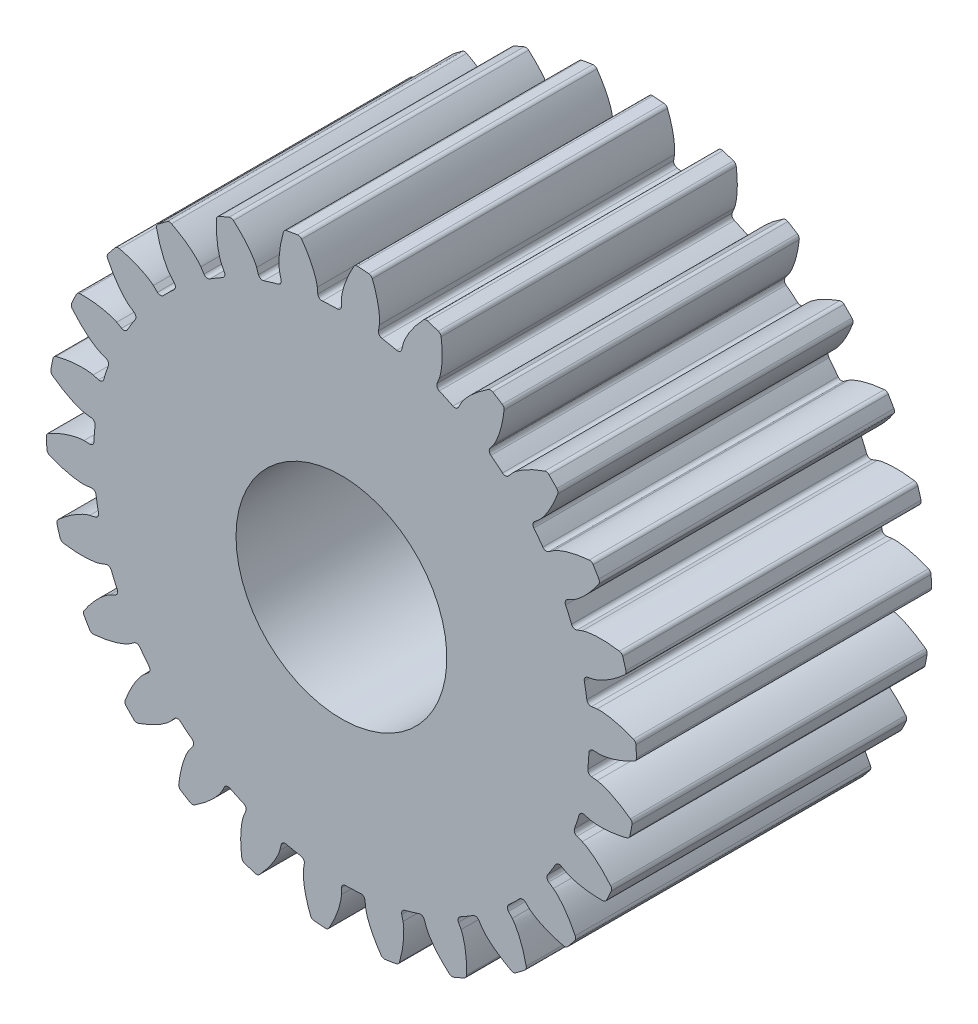
SolidWorks part; units mm, degrees
ref_plane "Front Plane" through (0, 0, 0) normal (0, 0, 1) x (1, 0, 0)
ref_plane "Top Plane" through (0, 0, 0) normal (0, 1, 0) x (1, 0, 0)
ref_plane "Right Plane" through (0, 0, 0) normal (1, 0, 0) x (0, 0, -1)
sketch "Involute Geometry" plane through (0, 0, 0) normal (0, 0, 1) x (1, 0, 0)
  line L0 (0, 12.216) -> (0, 0) construction
  line L1 (0, 0) -> (1.0333, 13.9618) construction
  line L2 (1.7984, 12.0829) -> (0, 0) construction
  line L3 (0.175, 12.9988) -> (0, 0) construction
  line L4 (0, 0) -> (1.7406, 12.883) construction
  circle A1 centre (0, 0) radius 12.216 construction
  circle A2 centre (0, 0) radius 13 construction
  circle A3 centre (0, 0) radius 14 construction
  circle A4 centre (0, 0) radius 11.75 construction
  arc A5 (0.6454, 13.9851) -> (1.4204, 13.9278) centre (0, 0) cw
  arc A6 (0.175, 12.9988) -> (1.7406, 12.883) centre (0, 0) cw construction
  spline S0 degree 4 poles (0, 12.216) (0, 12.2259) (0.0007, 12.2537) (0.0046, 12.3061) (0.0149, 12.3914) (0.0336, 12.4994) (0.064, 12.638) (0.108, 12.7997) (0.1647, 12.9755) (0.2354, 13.1642) (0.3138, 13.35) (0.3992, 13.5328) (0.4907, 13.7124) (0.6089, 13.9268) (0.7611, 14.1794) (0.9535, 14.4672) (1.1888, 14.7846) (1.4461, 15.0973) (1.7136, 15.3959) (1.9994, 15.6864) (2.287, 15.9594) (2.6008, 16.2305) (2.8982, 16.4744) (3.2472, 16.733) (3.5335, 16.9374) (3.9271, 17.1908) (4.1642, 17.3355) (4.4469, 17.4991) (4.5752, 17.5686) (4.654, 17.6115) knots 0 0 0 0 0 0.005377 0.015084 0.028532 0.04661 0.064855 0.092111 0.119476 0.146842 0.174209 0.201575 0.228941 0.256307 0.307035 0.361767 0.4165 0.471232 0.525964 0.580697 0.635429 0.690161 0.744894 0.799626 0.854358 0.909091 0.954545 1 1 1 1 1 construction
  spline S1 degree 4 poles (0, 12.216) (0, 12.2259) (0.0007, 12.2537) (0.0046, 12.3061) (0.0149, 12.3914) (0.0336, 12.4994) (0.064, 12.638) (0.108, 12.7997) (0.1647, 12.9755) (0.2354, 13.1642) (0.3138, 13.35) (0.3992, 13.5328) (0.4907, 13.7124) (0.6089, 13.9268) (0.7611, 14.1794) (0.9535, 14.4672) (1.1888, 14.7846) (1.4461, 15.0973) (1.7136, 15.3959) (1.9994, 15.6864) (2.287, 15.9594) (2.6008, 16.2305) (2.8982, 16.4744) (3.2472, 16.733) (3.5335, 16.9374) (3.8418, 17.1359) (3.9936, 17.2306) (4.0719, 17.2782) knots 0 0 0 0 0 0.005377 0.015084 0.028532 0.04661 0.064855 0.092111 0.119476 0.146842 0.174209 0.201575 0.228941 0.256307 0.307035 0.361767 0.4165 0.471232 0.525964 0.580697 0.635429 0.690161 0.744894 0.799626 0.854358 0.909091 0.909091 0.909091 0.909091 0.909091
  spline S3 degree 4 poles (1.7984, 12.0829) (1.7999, 12.0927) (1.8033, 12.1203) (1.8071, 12.1727) (1.8095, 12.2586) (1.8069, 12.3682) (1.7972, 12.5097) (1.7775, 12.6762) (1.7473, 12.8584) (1.7051, 13.0554) (1.655, 13.2507) (1.5974, 13.4441) (1.5334, 13.6352) (1.448, 13.8647) (1.3347, 14.1369) (1.1867, 14.45) (1.0007, 14.7985) (0.7922, 15.1457) (0.5716, 15.4804) (0.3317, 15.8098) (0.0874, 16.1222) (-0.1831, 16.4365) (-0.4413, 16.7215) (-0.7484, 17.0287) (-1.0015, 17.2731) (-1.3535, 17.5817) (-1.5667, 17.7597) (-1.8223, 17.9631) (-1.9389, 18.0507) (-2.0106, 18.1047) knots 0 0 0 0 0 0.005377 0.015084 0.028532 0.04661 0.064855 0.092111 0.119476 0.146842 0.174209 0.201575 0.228941 0.256307 0.307035 0.361767 0.4165 0.471232 0.525964 0.580697 0.635429 0.690161 0.744894 0.799626 0.854358 0.909091 0.954545 1 1 1 1 1 construction
  spline S4 degree 4 poles (1.7984, 12.0829) (1.7999, 12.0927) (1.8033, 12.1203) (1.8071, 12.1727) (1.8095, 12.2586) (1.8069, 12.3682) (1.7972, 12.5097) (1.7775, 12.6762) (1.7473, 12.8584) (1.7051, 13.0554) (1.655, 13.2507) (1.5974, 13.4441) (1.5334, 13.6352) (1.448, 13.8647) (1.3347, 14.1369) (1.1867, 14.45) (1.0007, 14.7985) (0.7922, 15.1457) (0.5716, 15.4804) (0.3317, 15.8098) (0.0874, 16.1222) (-0.1831, 16.4365) (-0.4413, 16.7215) (-0.7484, 17.0287) (-1.0015, 17.2731) (-1.2772, 17.5148) (-1.4134, 17.6308) (-1.4839, 17.6894) knots 0 0 0 0 0 0.005377 0.015084 0.028532 0.04661 0.064855 0.092111 0.119476 0.146842 0.174209 0.201575 0.228941 0.256307 0.307035 0.361767 0.4165 0.471232 0.525964 0.580697 0.635429 0.690161 0.744894 0.799626 0.854358 0.909091 0.909091 0.909091 0.909091 0.909091
  dimension "D5" = 6.923
sketch "Sketch2" plane through (0, 0, 0) normal (0, 0, 1) x (1, 0, 0)
  circle A0 centre (0, 0) radius 11.75 construction
  circle A1 centre (0, 0) radius 11.75
extrude "Boss-Extrude1" add sketch "Sketch2" along normal mid plane 14
sketch "Sketch3" plane through (0, 0, 0) normal (0, 0, 1) x (1, 0, 0)
  line L0 (0, 12.216) -> (0, 0) construction
  line L1 (1.7984, 12.0829) -> (0, 0) construction
  line L2 (0, 12.216) -> (0, 11.75)
  line L4 (1.7984, 12.0829) -> (1.7298, 11.622)
  circle A1 centre (0, 0) radius 11.75 construction
  arc A3 (0, 11.75) -> (1.7298, 11.622) centre (0, 0) cw
  arc A4 (1.4204, 13.9278) -> (0.6454, 13.9851) centre (0, 0) ccw construction
  arc A5 (1.4204, 13.9278) -> (0.6454, 13.9851) centre (0, 0) ccw
  spline S0 degree 4 poles (999.8581, 25.2356) (18.0155, 10.2173) (0.3577, 10.7107) (-0.0848, 11.5636) (0.0149, 12.3914) (0.0336, 12.4994) (0.064, 12.638) (0.108, 12.7997) (0.1647, 12.9755) (0.2354, 13.1642) (0.3138, 13.35) (0.3992, 13.5328) (0.4907, 13.7124) (0.6089, 13.9268) (0.7611, 14.1794) (0.9535, 14.4672) (1.1888, 14.7846) (1.4461, 15.0973) (1.7136, 15.3959) (1.9994, 15.6864) (2.287, 15.9594) (2.6008, 16.2305) (2.8982, 16.4744) (3.2472, 16.733) (4.4419, 17.5861) (8.1221, 19.6216) (-23.9178, -0.2396) (859.2438, 535.5339) knots -0.405932 -0.405932 -0.405932 -0.405932 -0.405932 0.005377 0.015084 0.028532 0.04661 0.064855 0.092111 0.119476 0.146842 0.174209 0.201575 0.228941 0.256307 0.307035 0.361767 0.4165 0.471232 0.525964 0.580697 0.635429 0.690161 0.744894 0.799626 0.854358 1.603617 1.603617 1.603617 1.603617 1.603617 only from (0, 12.216) to (3.8711, 11.595) construction
  spline S1 degree 4 poles (0, 12.216) (0, 12.2259) (0.0007, 12.2537) (0.0046, 12.3061) (0.0149, 12.3914) (0.0336, 12.4994) (0.064, 12.638) (0.108, 12.7997) (0.1647, 12.9755) (0.2354, 13.1642) (0.3138, 13.35) (0.3992, 13.5328) (0.4919, 13.7149) (0.5664, 13.8498) (0.6183, 13.9394) (0.6454, 13.9851) knots 0 0 0 0 0 0.005377 0.015084 0.028532 0.04661 0.064855 0.092111 0.119476 0.146842 0.174209 0.201575 0.228941 0.257808 0.257808 0.257808 0.257808 0.257808
  spline S3 degree 4 poles (-985.2487, 172.157) (-16.315, 12.7581) (1.223, 10.6467) (1.7863, 11.4251) (1.8095, 12.2586) (1.8069, 12.3682) (1.7972, 12.5097) (1.7775, 12.6762) (1.7473, 12.8584) (1.7051, 13.0554) (1.655, 13.2507) (1.5974, 13.4441) (1.5334, 13.6352) (1.448, 13.8647) (1.3347, 14.1369) (1.1867, 14.45) (1.0007, 14.7985) (0.7922, 15.1457) (0.5716, 15.4804) (0.3317, 15.8098) (0.0874, 16.1222) (-0.1831, 16.4365) (-0.4413, 16.7215) (-0.7484, 17.0287) (-1.8045, 18.0484) (-5.1449, 20.6035) (23.6219, -3.7581) (-771.0418, 656.1943) knots -0.405932 -0.405932 -0.405932 -0.405932 -0.405932 0.005377 0.015084 0.028532 0.04661 0.064855 0.092111 0.119476 0.146842 0.174209 0.201575 0.228941 0.256307 0.307035 0.361767 0.4165 0.471232 0.525964 0.580697 0.635429 0.690161 0.744894 0.799626 0.854358 1.603617 1.603617 1.603617 1.603617 1.603617 only from (1.7984, 12.0829) to (-1.4839, 17.6894) construction
  spline S4 degree 4 poles (1.7984, 12.0829) (1.7999, 12.0927) (1.8033, 12.1203) (1.8071, 12.1727) (1.8095, 12.2586) (1.8069, 12.3682) (1.7972, 12.5097) (1.7775, 12.6762) (1.7473, 12.8584) (1.7051, 13.0554) (1.655, 13.2507) (1.5974, 13.4441) (1.5325, 13.6379) (1.4787, 13.7823) (1.4405, 13.8785) (1.4204, 13.9278) knots 0 0 0 0 0 0.005377 0.015084 0.028532 0.04661 0.064855 0.092111 0.119476 0.146842 0.174209 0.201575 0.228941 0.257808 0.257808 0.257808 0.257808 0.257808
extrude "Boss-Extrude2" add sketch "Sketch3" along normal through all and the other way through all
fillet "Fillet2" [suppressed] radius 0.381
pattern_circular "CirPattern1" count 26 over 360 about axis through (0, 0, 7) along (0, 0, -1) of "Boss-Extrude2", "Fillet2"
ref_axis "Axis1" through (0, 0, 7) along (0, 0, -1)
sketch "Sketch4" plane through (0, 0, -7) normal (0, 0, -1) x (-1, 0, 0)
  circle A1 centre (0, 0) radius 5
  dimension "D1" = 10
extrude "Cut-Extrude1" cut sketch "Sketch4" against normal through all
fillet "Fillet3" radius 0.2 104 edges at (-8.5821, 8.0256, 0) (-9.6701, 6.6748, 0) (-10.9864, 4.1666, 0) (-11.3287, 3.1181, 0) (-11.6643, 1.4163, 0) (-11.7457, 0.3163, 0) (-11.6643, -1.4163, 0) (-11.4801, -2.5038, 0) (-10.9864, -4.1666, 0) (-10.5473, -5.1784, 0) (-9.6701, -6.6748, 0) (-9.0016, -7.5521, 0) (-7.7917, -8.795, 0) (-6.9327, -9.4869, 0) (-5.4605, -10.4041, 0) (-4.4609, -10.8703, 0) (-2.812, -11.4086, 0) (-1.7298, -11.622, 0) (0, -11.75, 0) (1.1018, -11.6982, 0) (2.812, -11.4086, 0) (3.8693, -11.0946, 0) (5.4605, -10.4041, 0) (6.412, -9.8462, 0) (7.7917, -8.795, 0) (8.5821, -8.0256, 0) (9.6701, -6.6748, 0) (10.2533, -5.7386, 0) (10.9864, -4.1666, 0) (11.3287, -3.1181, 0) (11.6643, -1.4163, 0) (11.7457, -0.3163, 0) (11.6643, 1.4163, 0) (11.4801, 2.5038, 0) (10.9864, 4.1666, 0) (10.5473, 5.1784, 0) (9.6701, 6.6748, 0) (9.0016, 7.5521, 0) (7.7917, 8.795, 0) (6.9327, 9.4869, 0) (5.4605, 10.4041, 0) (4.4609, 10.8703, 0) (2.812, 11.4086, 0) (1.7298, 11.622, 0) (0, 11.75, 0) (-10.2533, 5.7386, 0) (-1.1018, 11.6982, 0) (-2.812, 11.4086, 0) (-3.8693, 11.0946, 0) (-5.4605, 10.4041, 0) (-6.412, 9.8462, 0) (-7.7917, 8.795, 0) (1.4204, 13.9278, 0) (3.9735, 13.4243, 0) (4.7123, 13.1831, 0) (7.0707, 12.0833, 0) (7.7303, 11.6723, 0) (9.757, 10.04, 0) (10.299, 9.4831, 0) (11.8762, 7.4133, 0) (12.2692, 6.7429, 0) (13.3052, 4.3557, 0) (13.5264, 3.6107, 0) (13.9609, 1.045, 0) (13.9974, 0.2687, 0) (13.8053, -2.3265, 0) (13.655, -3.0889, 0) (12.8474, -5.5627, 0) (12.519, -6.267, 0) (11.1429, -8.4756, 0) (10.6554, -9.0809, 0) (8.7907, -10.896, 0) (8.1726, -11.367, 0) (5.9277, -12.6832, 0) (5.2148, -12.9925, 0) (2.7202, -13.7332, 0) (1.954, -13.863, 0) (-0.6454, -13.9851, 0) (-1.4204, -13.9278, 0) (-3.9735, -13.4243, 0) (-4.7123, -13.1831, 0) (-7.0707, -12.0833, 0) (-7.7303, -11.6723, 0) (-9.757, -10.04, 0) (-10.299, -9.4831, 0) (-11.8762, -7.4133, 0) (-12.2692, -6.7429, 0) (-13.3052, -4.3557, 0) (-13.5264, -3.6107, 0) (-13.9609, -1.045, 0) (-13.9974, -0.2687, 0) (-13.8053, 2.3265, 0) (-13.655, 3.0889, 0) (-12.8474, 5.5627, 0) (-12.519, 6.267, 0) (-11.1429, 8.4756, 0) (-10.6554, 9.0809, 0) (-8.7907, 10.896, 0) (-8.1726, 11.367, 0) (-5.9277, 12.6832, 0) (-5.2148, 12.9925, 0) (-2.7202, 13.7332, 0) (-1.954, 13.863, 0) (0.6454, 13.9851, 0)
equation "\"N\"= 26'Number of Teeth"
equation "\"m\"= 1mm'Diametral Pitch"
equation "\"phi\"= 20deg'Pressure Angle"
equation "\"a\"= \"m\"'Addendum"
equation "\"b\"= 1.25 * \"m\"'Dedendum"
equation "\"Dp\"= \"N\" * \"m\"'Pitch diameter"
equation "\"Db\"= \"Dp\" * cos ( \"phi\" )'Base diameter"
equation "\"D1@Involute Geometry\" = \"Db\""
equation "\"D2@Involute Geometry\" = \"Dp\""
equation "\"D3@Involute Geometry\" = \"Dp\" + 2 * \"a\""
equation "\"D4@Involute Geometry\" = \"Dp\" - 2 * \"b\""
equation "\"D1@CirPattern1\"=\"N\""
equation "\"D5@Involute Geometry\"=180/\"N\""
equation "\"D1@Boss-Extrude1\"=14*\"m\""
equation "\"alpha\"= sqr ( \"Dp\" ^ 2 - \"Db\" ^ 2 ) / \"Db\" * 180 / pi - \"phi\""
equation "\"beta\"= ( ( 360deg / \"N\" ) / 4 - \"alpha\" )"
